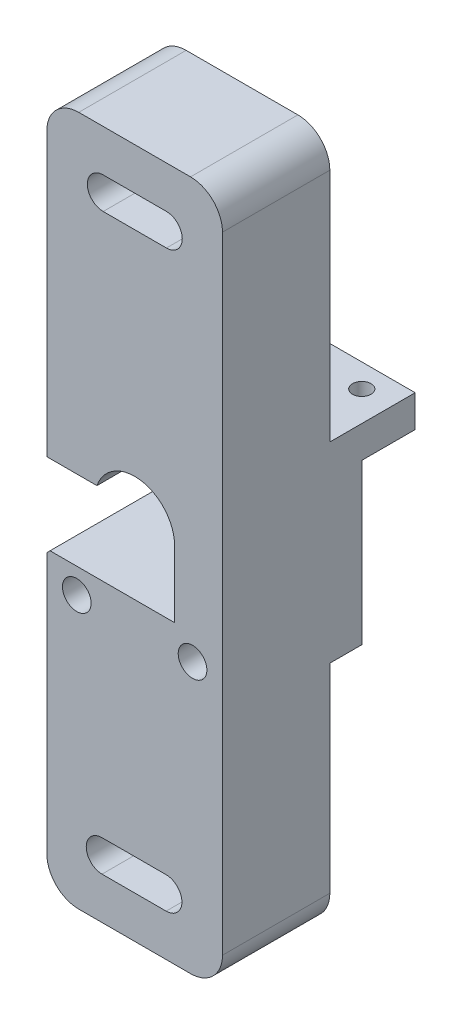
SolidWorks part; units mm, degrees
material "ABS"
ref_plane "Front Plane" through (0, 0, 0) normal (0, 0, 1) x (1, 0, 0)
ref_plane "Top Plane" through (0, 0, 0) normal (0, 1, 0) x (1, 0, 0)
ref_plane "Right Plane" through (0, 0, 0) normal (1, 0, 0) x (0, 0, -1)
ref_plane "Plane1" through (0, 0, 33.655) normal (0, 0, 1) x (1, 0, 0)
sketch "Sketch1" plane through (0, 0, 33.655) normal (0, 0, 1) x (1, 0, 0)
  line L0 (-13.97, 9.8105) -> (-13.462, 9.8105)
  line L1 (-13.462, 9.8105) -> (-13.462, 10.3185)
  line L2 (-13.462, 10.3185) -> (-13.97, 9.8105)
extrude "Boss-Extrude1" add sketch "Sketch1" against normal blind 5.08
sketch "Sketch2" plane through (-13.462, 0, 0) normal (1, 0, 0) x (0, 0, -1)
  line L0 (-33.655, 10.3185) -> (-28.575, 10.3185)
  line L1 (-28.575, 10.3185) -> (-28.575, 9.8105)
  line L2 (-28.575, 9.8105) -> (-33.655, 9.8105)
  line L3 (-33.655, 9.8105) -> (-33.655, 10.3185)
extrude "Boss-Extrude2" add sketch "Sketch2" along normal blind 17.907
sketch "Sketch3" plane through (4.445, 0, 0) normal (1, 0, 0) x (0, 0, -1)
  line L0 (-28.575, 9.8105) -> (-33.655, 9.8105)
  line L1 (-33.655, 9.8105) -> (-33.655, 10.3185)
  line L2 (-33.655, 10.3185) -> (-29.083, 10.3185)
  line L3 (-29.083, 10.3185) -> (-28.575, 10.8265)
  line L4 (-28.575, 10.8265) -> (-28.575, 9.8105)
extrude "Boss-Extrude3" add sketch "Sketch3" along normal blind 1.905
sketch "Sketch4" plane through (0, 0, 28.575) normal (0, 0, -1) x (-1, 0, 0)
  line L0 (-6.35, 9.8105) -> (-6.35, 27.303)
  line L1 (-6.35, 27.303) -> (3.937, 27.303)
  line L2 (3.937, 27.303) -> (3.937, 23.0185)
  line L3 (-3.937, 23.0185) -> (-4.445, 23.0185)
  line L4 (-4.445, 23.0185) -> (-4.445, 10.3185)
  line L5 (-4.445, 10.3185) -> (13.462, 10.3185)
  line L6 (13.462, 10.3185) -> (13.97, 9.8105)
  line L7 (13.97, 9.8105) -> (-6.35, 9.8105)
  arc A0 (3.937, 23.0185) -> (-3.937, 23.0185) centre (0, 20.955) ccw
extrude "Boss-Extrude4" add sketch "Sketch4" along normal blind 17.78
sketch "Sketch5" plane through (0, 9.8105, 0) normal (0, -1, 0) x (1, 0, 0)
  line L0 (6.35, 10.795) -> (-13.97, 10.795)
  line L1 (-13.97, 10.795) -> (-13.97, 33.655)
  line L2 (-13.97, 33.655) -> (6.35, 33.655)
  line L3 (6.35, 33.655) -> (6.35, 10.795)
extrude "Boss-Extrude5" add sketch "Sketch5" along normal blind 63.1505
sketch "Sketch6" plane through (-3.937, 0, 0) normal (-1, 0, 0) x (0, 0, 1)
  line L0 (28.575, 23.0185) -> (10.795, 23.0185)
  line L1 (10.795, 23.0185) -> (10.795, 27.303)
  line L2 (10.795, 27.303) -> (28.575, 27.303)
  line L3 (28.575, 27.303) -> (28.575, 23.0185)
extrude "Boss-Extrude6" add sketch "Sketch6" along normal blind 10.033
sketch "Sketch7" plane through (0, 0, 28.575) normal (0, 0, 1) x (1, 0, 0)
  line L0 (0.1584, 27.303) -> (6.35, 27.303)
  line L1 (6.35, 27.303) -> (6.35, 20.955)
  arc A0 (6.35, 20.955) -> (0.1584, 27.303) centre (0, 20.955) ccw
extrude "Boss-Extrude7" add sketch "Sketch7" along normal blind 5.08
sketch "Sketch8" plane through (6.35, 0, 0) normal (1, 0, 0) x (0, 0, -1)
  line L0 (-10.795, 27.303) -> (-10.795, -53.34)
  line L1 (-10.795, -53.34) -> (-33.655, -53.34)
  line L2 (-33.655, -53.34) -> (-33.655, 27.303)
  line L3 (-33.655, 27.303) -> (-10.795, 27.303)
extrude "Boss-Extrude8" add sketch "Sketch8" along normal blind 7.62
sketch "Sketch9" plane through (0, 0, 10.795) normal (0, 0, -1) x (-1, 0, 0)
  line L0 (13.97, 25.4) -> (4.445, 25.4)
  line L1 (4.445, 25.4) -> (4.445, 23.5265)
  line L2 (4.445, 23.5265) -> (3.937, 23.0185)
  line L3 (3.937, 23.0185) -> (13.97, 23.0185)
  line L4 (13.97, 23.0185) -> (13.97, 25.4)
extrude "Cut-Extrude1" cut sketch "Sketch9" against normal blind 12.7
sketch "Sketch10" plane through (0, 0, 10.795) normal (0, 0, -1) x (-1, 0, 0)
  line L0 (-4.445, 10.3185) -> (-4.445, 23.0185)
  line L1 (-4.445, 23.0185) -> (-13.97, 23.0185)
  line L2 (-13.97, 23.0185) -> (-13.97, -53.34)
  line L3 (-13.97, -53.34) -> (13.97, -53.34)
  line L4 (13.97, -53.34) -> (13.97, 9.8105)
  line L5 (13.97, 9.8105) -> (13.462, 10.3185)
  line L6 (13.462, 10.3185) -> (-4.445, 10.3185)
extrude "Cut-Extrude2" cut sketch "Sketch10" against normal blind 12.7
sketch "Sketch11" plane through (0, 0, 28.575) normal (0, 0, 1) x (1, 0, 0)
  line L0 (-6.0054, 23.0185) -> (-13.97, 23.0185)
  line L1 (-13.97, 23.0185) -> (-13.97, 27.303)
  line L2 (-13.97, 27.303) -> (-0.1584, 27.303)
  arc A0 (-0.1584, 27.303) -> (-6.0054, 23.0185) centre (0, 20.955) ccw
extrude "Boss-Extrude9" add sketch "Sketch11" along normal blind 5.08
sketch "Sketch12" plane through (0, 27.303, 0) normal (0, 1, 0) x (-1, 0, 0)
  line L0 (-13.97, 33.655) -> (13.97, 33.655)
  line L1 (13.97, 33.655) -> (13.97, 10.795)
  line L2 (13.97, 10.795) -> (-13.97, 10.795)
  line L3 (-13.97, 10.795) -> (-13.97, 33.655)
extrude "Boss-Extrude10" add sketch "Sketch12" along normal blind 62.232
sketch "Sketch13" plane through (0, 23.0185, 0) normal (0, -1, 0) x (1, 0, 0)
  line L0 (13.97, 10.795) -> (13.97, 23.495)
  line L1 (13.97, 23.495) -> (4.445, 23.495)
  line L2 (4.445, 23.495) -> (4.445, 10.795)
  line L3 (4.445, 10.795) -> (13.97, 10.795)
extrude "Cut-Extrude3" cut sketch "Sketch13" against normal blind 2.3815
sketch "Sketch14" plane through (13.97, 0, 0) normal (1, 0, 0) x (0, 0, -1)
  line L0 (-28.575, 30.48) -> (-10.795, 30.48)
  line L1 (-10.795, 30.48) -> (-10.795, 89.535)
  line L2 (-10.795, 89.535) -> (-28.575, 89.535)
  line L3 (-28.575, 89.535) -> (-28.575, 30.48)
extrude "Cut-Extrude4" cut sketch "Sketch14" against normal through all
sketch "Sketch15" plane through (13.97, 0, 0) normal (1, 0, 0) x (0, 0, -1)
  line L0 (-23.495, 0) -> (-28.575, 0)
  line L1 (-28.575, 0) -> (-28.575, -53.34)
  line L2 (-28.575, -53.34) -> (-23.495, -53.34)
  line L3 (-23.495, -53.34) -> (-23.495, 0)
extrude "Cut-Extrude5" cut sketch "Sketch15" against normal through all
sketch "Sketch16" plane through (0, 0, 28.575) normal (0, 0, -1) x (-1, 0, 0)
  line L0 (5.08, -41.5925) -> (-5.08, -41.5925)
  line L1 (-5.08, -46.6725) -> (5.08, -46.6725)
  arc A0 (5.08, -46.6725) -> (5.08, -41.5925) centre (5.08, -44.1325) ccw
  arc A1 (-5.08, -41.5925) -> (-5.08, -46.6725) centre (-5.08, -44.1325) ccw
extrude "Cut-Extrude6" cut sketch "Sketch16" against normal through all
sketch "Sketch17" plane through (0, 0, 33.655) normal (0, 0, 1) x (1, 0, 0)
  line L0 (-5.08, -38.4175) -> (5.08, -38.4175)
  line L1 (5.08, -33.3375) -> (-5.08, -33.3375)
  arc A0 (5.08, -38.4175) -> (5.08, -33.3375) centre (5.08, -35.8775) ccw
  arc A1 (-5.08, -33.3375) -> (-5.08, -38.4175) centre (-5.08, -35.8775) ccw
extrude "Cut-Extrude7" cut sketch "Sketch17" against normal through all
sketch "Sketch18" plane through (0, 0, 28.575) normal (0, 0, -1) x (-1, 0, 0)
  line L0 (5.08, 73.9775) -> (-5.08, 73.9775)
  line L1 (-5.08, 68.8975) -> (5.08, 68.8975)
  arc A0 (5.08, 68.8975) -> (5.08, 73.9775) centre (5.08, 71.4375) ccw
  arc A1 (-5.08, 73.9775) -> (-5.08, 68.8975) centre (-5.08, 71.4375) ccw
extrude "Cut-Extrude8" cut sketch "Sketch18" against normal through all
sketch "Sketch19" plane through (0, 0, 28.575) normal (0, 0, -1) x (-1, 0, 0)
  line L0 (5.08, 82.2325) -> (-5.08, 82.2325)
  line L1 (-5.08, 77.1525) -> (5.08, 77.1525)
  arc A0 (5.08, 77.1525) -> (5.08, 82.2325) centre (5.08, 79.6925) ccw
  arc A1 (-5.08, 82.2325) -> (-5.08, 77.1525) centre (-5.08, 79.6925) ccw
extrude "Cut-Extrude9" cut sketch "Sketch19" against normal through all
hole_wizard "CBORE for M2.5 Hex Head Machine Screw1" positions "Sketch21" profile "Sketch20" counterbore size "M2.5" standard "ANSI Metric"
sketch "Sketch21" plane through (0, 0, 33.655) normal (0, 0, 1) x (1, 0, 0)
  point P0 (9.2075, 6.35)
  point P1 (-9.2075, 6.35)
sketch "Sketch20" plane through (9.2075, 6.35, 33.655) normal (1, 0, 0) x (0, -1, 0)
  line L0 (0, 0) -> (0, 22.86)
  line L1 (0, 22.86) -> (1.4732, 22.86)
  line L3 (1.4732, 22.86) -> (1.4732, 2.8448)
  line L4 (1.4732, 2.8448) -> (2.7788, 2.8448)
  line L5 (2.7788, 2.8448) -> (2.7788, 0)
  line L7 (2.7788, 0) -> (0, 0)
  line L11 (0, -6.35) -> (0, 107.95) construction
  dimension "Thru Hole Dia." = 2.9464
  dimension "Thru Hole Depth" = 22.86
  dimension "C'Bore Dia." = 5.5575
  dimension "C'Bore Depth" = 2.8448
hole_wizard "M2.5 Clearance Hole1" positions "Sketch23" profile "Sketch22" hole size "M2.5" standard "ANSI Metric"
sketch "Sketch23" plane through (0, 30.48, 0) normal (0, 1, 0) x (1, 0, 0)
  point P0 (9.2075, -18.7325)
sketch "Sketch22" plane through (9.2075, 30.48, 18.7325) normal (1, 0, 0) x (0, 0, 1)
  line L0 (0, 0) -> (0, 83.82)
  line L1 (0, 83.82) -> (1.4732, 83.82)
  line L2 (1.4732, 83.82) -> (1.4732, 0)
  line L5 (1.4732, 0) -> (0, 0)
  line L11 (0, -6.35) -> (0, 107.95) construction
  dimension "Thru Hole Dia." = 2.9464
  dimension "Thru Hole Depth" = 83.82
hole_wizard "M2.5 Clearance Hole2" positions "Sketch25" profile "Sketch24" hole size "M2.5" standard "ANSI Metric"
sketch "Sketch25" plane through (0, 25.4, 0) normal (0, -1, 0) x (-1, 0, 0)
  point P0 (9.2075, -18.7325)
sketch "Sketch24" plane through (-9.2075, 25.4, 18.7325) normal (1, 0, 0) x (0, 0, -1)
  line L0 (0, 0) -> (0, 64.135)
  line L1 (0, 64.135) -> (1.4732, 64.135)
  line L2 (1.4732, 64.135) -> (1.4732, 0)
  line L5 (1.4732, 0) -> (0, 0)
  line L11 (0, -6.35) -> (0, 107.95) construction
  dimension "Thru Hole Dia." = 2.9464
  dimension "Thru Hole Depth" = 64.135
fillet "Fillet2" radius 2.54 1 edges at (4.445, 10.3185, 26.289) tangent propagation no
chamfer "Chamfer2" distance 0.938 angle 45 2 edges at (4.5458, 25.3888, 28.575) (6.35, 15.8908, 28.575)
fillet "Fillet3" radius 5.08 4 edges at (13.97, -53.34, 31.115) (-13.97, -53.34, 31.115) (13.97, 89.535, 31.115) (-13.97, 89.535, 31.115) tangent propagation no
sketch "Sketch31" plane through (0, 0, 33.655) normal (0, 0, 1) x (1, 0, 0)
  line L0 (13.97, -53.34) -> (13.97, 89.535) construction
  line L1 (13.97, 89.535) -> (13.97, 73.0437) construction
  line L2 (13.97, -53.34) -> (13.97, -36.82) construction
  line L3 (0, -53.34) -> (0, -46.6725) construction
  line L4 (8.89, -53.34) -> (-8.89, -53.34) construction
  line L5 (5.08, -46.6725) -> (-5.08, -46.6725) construction
  line L6 (-5.08, -38.4175) -> (5.08, -38.4175) construction
  line L7 (-5.08, -38.4175) -> (5.08, -38.4175)
  line L8 (5.08, -33.3375) -> (-5.08, -33.3375)
  line L9 (0, 89.535) -> (0, 73.9775) construction
  line L10 (-8.89, 89.535) -> (8.89, 89.535) construction
  line L11 (-5.08, 73.9775) -> (5.08, 73.9775) construction
  arc A2 (-5.08, -33.3375) -> (-5.08, -38.4175) centre (-5.08, -35.8775) ccw construction
  arc A3 (5.08, -33.3375) -> (5.08, -38.4175) centre (5.08, -35.8775) cw
  arc A4 (-5.08, -33.3375) -> (-5.08, -38.4175) centre (-5.08, -35.8775) ccw
extrude "Boss-Extrude16" add sketch "Sketch31" against normal blind 5.08
sketch "Sketch33" plane through (0, 0, 33.655) normal (0, 0, 1) x (1, 0, 0)
  line L0 (0, -53.34) -> (13.97, -53.34) construction
  line L1 (8.89, -53.34) -> (-8.89, -53.34) construction
  line L2 (13.97, -53.34) -> (13.97, -36.7706) construction
  line L3 (13.97, 84.455) -> (13.97, -48.26) construction
  line L4 (13.97, -36.7706) -> (-13.97, -36.7706) construction
  line L5 (-13.97, -48.26) -> (-13.97, 9.8105) construction
  line L6 (-13.97, -36.7706) -> (-13.97, -53.34) construction
  line L7 (-13.97, -53.34) -> (13.97, -53.34) construction
  line L9 (13.97, -36.7706) -> (-13.97, -36.7706)
  line L10 (13.97, -36.7706) -> (13.97, -53.34)
  line L11 (13.97, -53.34) -> (-13.97, -53.34)
  line L12 (-13.97, -36.7706) -> (-13.97, -53.34)
extrude "Cut-Extrude10" cut sketch "Sketch33" against normal blind 5.08
sketch "Sketch34" plane through (0, 0, 33.655) normal (0, 0, 1) x (1, 0, 0)
  line L0 (0, 89.535) -> (13.97, 89.535) construction
  line L1 (-8.89, 89.535) -> (8.89, 89.535) construction
  line L2 (13.97, 89.535) -> (13.97, 73.1281) construction
  line L3 (13.97, 84.455) -> (13.97, -36.7706) construction
  line L4 (-5.08, 73.9775) -> (5.08, 73.9775)
  line L5 (-5.08, 68.8975) -> (5.08, 68.8975)
  arc A0 (5.08, 73.9775) -> (5.08, 68.8975) centre (5.08, 71.4375) cw
  arc A1 (5.08, 68.8975) -> (5.08, 73.9775) centre (5.08, 71.4375) ccw construction
  arc A2 (-5.08, 73.9775) -> (-5.08, 68.8975) centre (-5.08, 71.4375) ccw
extrude "Boss-Extrude17" add sketch "Sketch34" against normal blind 5.08
sketch "Sketch35" plane through (0, 0, 33.655) normal (0, 0, 1) x (1, 0, 0)
  line L0 (0, 89.535) -> (13.97, 89.535) construction
  line L1 (-8.89, 89.535) -> (8.89, 89.535) construction
  line L2 (13.97, 89.535) -> (13.97, 73.0056) construction
  line L3 (13.97, 84.455) -> (13.97, -36.7706) construction
  line L4 (13.97, 73.0056) -> (-13.97, 73.0056) construction
  line L5 (-13.97, 84.455) -> (-13.97, 23.0185) construction
  line L6 (-13.97, 73.0056) -> (-13.97, 89.535) construction
  line L7 (-13.97, 89.535) -> (0, 89.535) construction
  line L9 (13.97, 73.0056) -> (-13.97, 73.0056)
  line L10 (13.97, 73.0056) -> (13.97, 89.535)
  line L11 (13.97, 89.535) -> (-13.97, 89.535)
  line L12 (-13.97, 73.0056) -> (-13.97, 89.535)
extrude "Cut-Extrude11" cut sketch "Sketch35" against normal blind 5.08
sketch "Sketch37" plane through (0, 0, 33.655) normal (0, 0, 1) x (1, 0, 0)
  line L0 (0, 73.0056) -> (0, 66.325) construction
  line L1 (-13.97, 73.0056) -> (13.97, 73.0056) construction
  line L2 (0, 66.325) -> (5.0537, 66.325) construction
  line L3 (5.0537, 66.325) -> (-5.0058, 66.325) construction
  line L4 (0, 66.325) -> (0, 61.2854) construction
  line L5 (5.0537, 61.2854) -> (-5.0058, 61.2854)
  line L6 (-5.0058, 66.325) -> (5.0537, 66.325)
  arc A0 (5.0537, 66.325) -> (5.0537, 61.2854) centre (5.0537, 63.8052) cw
  arc A1 (-5.0058, 66.325) -> (-5.0058, 61.2854) centre (-5.0058, 63.8052) ccw
extrude "Cut-Extrude12" cut sketch "Sketch37" against normal blind 5.08
fillet "Fillet4" radius 5.08 1 edges at (13.97, 73.0056, 31.115)
fillet "Fillet5" radius 5.08 1 edges at (-13.97, 73.0056, 31.115)
fillet "Fillet6" radius 5.08 1 edges at (13.97, -36.7706, 31.115)
fillet "Fillet7" radius 5.08 1 edges at (-13.97, -36.7706, 31.115)
sketch "Sketch38" plane through (0, 0, 33.655) normal (0, 0, 1) x (1, 0, 0)
  line L0 (0, -36.7706) -> (0, -30.0977) construction
  line L1 (8.89, -36.7706) -> (-8.89, -36.7706) construction
  line L2 (0, -30.0977) -> (5.0095, -30.0977) construction
  line L3 (5.0095, -30.0977) -> (-5.1915, -30.0977) construction
  line L4 (0, -30.0977) -> (0, -25.0773) construction
  line L5 (5.0095, -25.0773) -> (-5.1915, -25.0773)
  line L6 (-5.1915, -30.0977) -> (5.0095, -30.0977)
  arc A0 (5.0095, -25.0773) -> (5.0095, -30.0977) centre (5.0095, -27.5875) cw
  arc A1 (-5.1915, -25.0773) -> (-5.1915, -30.0977) centre (-5.1915, -27.5875) ccw
extrude "Cut-Extrude13" cut sketch "Sketch38" against normal blind 5.08
sketch "Sketch39" plane through (0, 30.48, 0) normal (0, 1, 0) x (1, 0, 0)
  line L0 (-13.97, -10.795) -> (-13.97, -14.3832)
  line L1 (-13.97, -28.575) -> (-13.97, -10.795) construction
  line L2 (-13.97, -14.3832) -> (13.97, -14.3832)
  line L3 (13.97, -28.575) -> (13.97, -10.795) construction
  line L4 (13.97, -14.3832) -> (13.97, -10.795)
  line L5 (13.97, -10.795) -> (-13.97, -10.795)
extrude "Cut-Extrude14" cut sketch "Sketch39" against normal blind 7.493
sketch "Sketch40" plane through (0, 30.48, 0) normal (0, 1, 0) x (1, 0, 0)
  line L0 (-13.97, -14.3832) -> (-13.97, -15.002)
  line L1 (-13.97, -28.575) -> (-13.97, -14.3832) construction
  line L2 (-13.97, -15.002) -> (13.97, -15.002)
  line L3 (13.97, -28.575) -> (13.97, -14.3832) construction
  line L4 (13.97, -15.002) -> (13.97, -14.3832)
  line L5 (13.97, -14.3832) -> (-13.97, -14.3832)
extrude "Cut-Extrude15" cut sketch "Sketch40" against normal blind 7.493
sketch "Sketch41" plane through (0, 0, 33.655) normal (0, 0, 1) x (1, 0, 0)
  line L0 (-5.0058, 66.325) -> (5.0537, 66.325)
  line L1 (-8.89, -36.7706) -> (8.89, -36.7706)
  line L2 (-13.97, -31.6906) -> (-13.97, 9.8105)
  line L3 (-8.89, 73.0056) -> (8.89, 73.0056)
  line L4 (13.97, -31.6906) -> (13.97, 67.9256)
  line L5 (-13.97, -36.7706) -> (13.97, 73.0056) construction
  line L6 (-13.97, 73.0056) -> (13.97, -36.7706) construction
  line L7 (-5.0058, 61.2854) -> (5.0537, 61.2854)
  line L8 (0, 18.1175) -> (9.8157, 18.1175) construction
  line L11 (-5.1915, -25.0773) -> (-5.1915, -30.0977) construction
  line L12 (5.0095, -30.0977) -> (-5.1915, -30.0977)
  line L13 (5.0095, -25.0773) -> (-5.1915, -25.0773) construction
  line L14 (-5.1915, -25.0773) -> (5.0095, -25.0773)
  line L15 (-13.97, 23.0185) -> (-6.0054, 23.0185)
  line L16 (-13.97, 9.8105) -> (-13.462, 10.3185)
  line L17 (-13.462, 10.3185) -> (1.905, 10.3185)
  line L18 (-13.97, 23.0185) -> (-13.97, 67.9256)
  line L19 (6.35, 20.955) -> (6.35, 10.3185)
  line L20 (6.35, 10.3185) -> (1.905, 10.3185)
  arc A0 (-8.89, -36.7706) -> (-13.97, -31.6906) centre (-8.89, -31.6906) cw
  arc A1 (8.89, -36.7706) -> (13.97, -31.6906) centre (8.89, -31.6906) ccw
  arc A2 (8.89, 73.0056) -> (13.97, 67.9256) centre (8.89, 67.9256) cw
  arc A3 (-13.97, 67.9256) -> (-8.89, 73.0056) centre (-8.89, 67.9256) cw
  arc A4 (-5.0058, 66.325) -> (-5.0058, 61.2854) centre (-5.0058, 63.8052) ccw
  arc A5 (5.0537, 61.2854) -> (5.0537, 66.325) centre (5.0537, 63.8052) ccw
  arc A8 (-5.1915, -25.0773) -> (-5.1915, -30.0977) centre (-5.1915, -27.5875) ccw construction
  arc A9 (-5.1915, -25.0773) -> (-5.1915, -30.0977) centre (-5.1915, -27.5875) ccw
  arc A10 (-6.0054, 23.0185) -> (6.0054, 23.0185) centre (0, 20.9521) cw
  arc A11 (5.0095, -30.0977) -> (5.0095, -25.0773) centre (5.0095, -27.5875) ccw construction
  arc A12 (5.0095, -30.0977) -> (5.0095, -25.0773) centre (5.0095, -27.5875) ccw
  arc A13 (6.35, 20.955) -> (0.1584, 27.303) centre (0, 20.955) ccw construction
  arc A14 (6.0054, 23.0185) -> (6.35, 20.955) centre (0.0165, 20.9578) cw
  circle A15 centre (-9.2075, 6.35) radius 2.7788
  circle A16 centre (9.2075, 6.35) radius 2.7788
  point P0 (0, 18.1175)
  dimension "D1" = 5.08
extrude "Boss-Extrude18" add sketch "Sketch41" along normal blind 12
sketch "Sketch42" plane through (0, 0, 45.655) normal (0, 0, 1) x (1, 0, 0)
  circle A0 centre (-9.2075, 6.35) radius 2.7788
  circle A1 centre (9.2075, 6.35) radius 2.7788
extrude "Cut-Extrude16" cut sketch "Sketch42" against normal blind 32.512
sketch "Sketch43" plane through (0, 0, 45.655) normal (0, 0, 1) x (1, 0, 0)
  circle A0 centre (-9.2075, 6.35) radius 2.7788
  circle A1 centre (9.2075, 6.35) radius 2.7788
  circle A2 centre (-9.2075, 6.35) radius 2.2788
  circle A3 centre (9.2075, 6.35) radius 2.2788
  dimension "D1" = 0.5
  dimension "D2" = 0.5
extrude "Boss-Extrude19" add sketch "Sketch43" against normal up to surface (22.16 mm away) up to face at (-6.4287, 6.35, 23.495)
